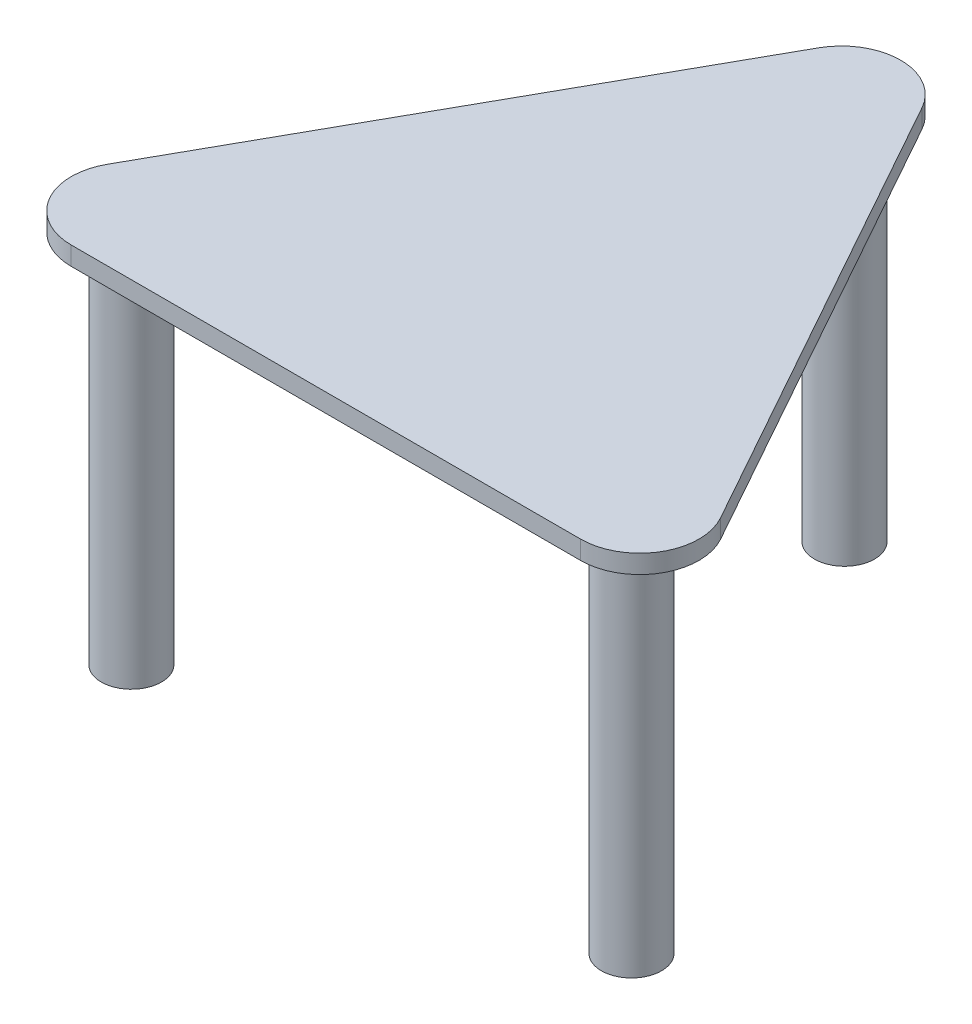
SolidWorks part; units mm, degrees
ref_plane "Front Plane" through (0, 0, 0) normal (0, 0, 1) x (1, 0, 0)
ref_plane "Top Plane" through (0, 0, 0) normal (0, 1, 0) x (1, 0, 0)
ref_plane "Right Plane" through (0, 0, 0) normal (1, 0, 0) x (0, 0, -1)
sketch "Sketch1" plane through (0, 0, 0) normal (0, 1, 0) x (1, 0, 0)
  line L0 (-46.5262, 35.6116) -> (-74.0247, -13.6566)
  line L1 (-68.4363, -23.1757) -> (-13.4392, -23.1757)
  line L2 (-7.8507, -13.6566) -> (-35.3493, 35.6116)
  circle A0 centre (-13.9377, -17.1757) radius 1.25
  circle A1 centre (-67.9377, -17.1757) radius 1.25
  circle A2 centre (-40.9377, 32.8243) radius 1.25
  circle A3 centre (-13.9377, -17.1757) radius 3.25
  circle A4 centre (-67.9377, -17.1757) radius 3.25
  circle A5 centre (-40.9377, 32.8243) radius 3.25
  arc A6 (-35.3493, 35.6116) -> (-46.5262, 35.6116) centre (-40.9377, 32.4925) ccw
  arc A7 (-68.4363, -23.1757) -> (-74.0247, -13.6566) centre (-68.4363, -16.7757) cw
  arc A8 (-13.4392, -23.1757) -> (-7.8507, -13.6566) centre (-13.4392, -16.7757) ccw
  point P8 (-40.9377, -23.1757)
  point P18 (-40.9377, 45.6243)
  point P21 (-79.3377, -23.1757)
  point P24 (-2.5377, -23.1757)
  dimension "D1" = 2.5
  dimension "D2" = 6.5
  dimension "D3" = 2.5
  dimension "D4" = 6.5
  dimension "D5" = 2.5
  dimension "D6" = 6.5
  dimension "D13" = 6.4
  dimension "D14" = 6.4
  dimension "D15" = 6.4
  dimension "D7" = 50
  dimension "D8" = 27
  dimension "D9" = 27
  dimension "D10" = 76.8
  dimension "D11" = 68.8
  dimension "D12" = 12.8
extrude "Boss-Extrude1" add sketch "Sketch1" along normal blind 2 contours L1 A8 L2 A6 L0 A7 A3 A4 A5 | A5 A2 | A2 | A3 A0 | A0 | A4 A1 | A1 region at (-40.9377, 0, 0.2738) region at (-13.9377, 0, 17.1757) region at (-67.9377, 0, 17.1757) region at (-40.9377, 0, -32.8243) region at (-17.0958, 0, 17.1757) region at (-71.0958, 0, 17.1757) region at (-44.0958, 0, -32.8243)
extrude "Boss-Extrude2" add sketch "Sketch1<3>" against normal blind 40 contours A5 A2 | A4 A1 | A3 A0 region at (-17.0958, 0, 17.1757) region at (-71.0958, 0, 17.1757) region at (-44.0958, 0, -32.8243)
sketch "Sketch1<3>" plane through (0, 0, 0) normal (0, 1, 0) x (1, 0, 0) same geometry as "Sketch1"
sketch "Sketch2" plane through (0, 0, 0) normal (0, -1, 0) x (1, 0, 0)
  line L0 (-15.473, 0) -> (-66.4024, 0) construction
  line L1 (-7.8507, 13.6566) -> (-35.3493, -35.6116) construction
  line L2 (-46.5262, -35.6116) -> (-74.0247, 13.6566) construction
  text T0 "GPS\r\nthis side down"
extrude "Boss-Extrude3" add sketch "Sketch2" along normal blind 1
